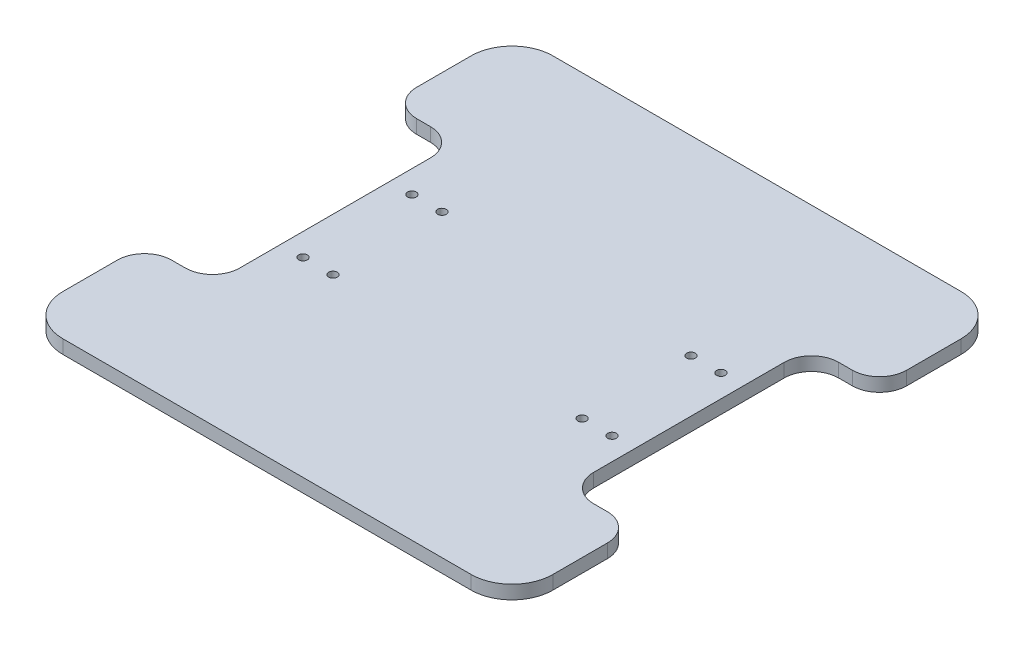
SolidWorks part; units mm, degrees
ref_plane "Спереди" through (0, 0, 0) normal (0, 0, 1) x (1, 0, 0)
ref_plane "Сверху" through (0, 0, 0) normal (0, 1, 0) x (1, 0, 0)
ref_plane "Справа" through (0, 0, 0) normal (1, 0, 0) x (0, 0, -1)
sketch "Sketch1" plane through (0, 0, 0) normal (0, 1, 0) x (1, 0, 0)
  line L1 (-90, 90) -> (90, 90)
  line L2 (-90, 90) -> (-90, -90)
  line L3 (-90, -90) -> (90, -90)
  line L4 (90, 90) -> (90, -90)
  line L5 (-90, 90) -> (90, -90) construction
  line L6 (-90, -90) -> (90, 90) construction
  point P0 (0, 0)
  dimension "D1" = 180
  dimension "D2" = 180
extrude "Boss-Extrude1" add sketch "Sketch1" along normal blind 5
fillet "Fillet1" radius 15 4 edges at (-90, 2.5, -90) (90, 2.5, -90) (-90, 2.5, 90) (90, 2.5, 90)
sketch "Sketch2" plane through (0, 5, 0) normal (0, 1, 0) x (1, 0, 0)
  line L0 (0, 0) -> (-77.5, 0) construction
  line L1 (2.75, 0) -> (-2.75, 0) construction
  line L2 (-90, 75) -> (-90, -75) construction
  line L3 (-90, 45) -> (-65, 45)
  line L4 (-90, 45) -> (-90, -45)
  line L5 (-90, -45) -> (-65, -45)
  line L6 (-65, 45) -> (-65, -45)
  line L7 (-90, 45) -> (-65, -45) construction
  line L8 (-90, -45) -> (-65, 45) construction
  line L9 (0, 0) -> (0, 45) construction
  line L10 (90, -45) -> (65, 45) construction
  line L11 (90, 45) -> (65, -45) construction
  line L12 (65, 45) -> (65, -45)
  line L13 (90, -45) -> (65, -45)
  line L14 (90, 45) -> (90, -45)
  line L15 (90, 45) -> (65, 45)
  circle A0 centre (-56.75, 20) radius 1.6
  circle A1 centre (-45.75, 20) radius 1.6
  circle A2 centre (-56.75, -20) radius 1.6
  circle A3 centre (-45.75, -20) radius 1.6
  circle A4 centre (45.75, 20) radius 1.6
  circle A5 centre (56.75, 20) radius 1.6
  circle A6 centre (45.75, -20) radius 1.6
  circle A7 centre (56.75, -20) radius 1.6
  dimension "D1" = 25
  dimension "D2" = 90
extrude "Cut-Extrude2" cut sketch "Sketch2" against normal through all
fillet "Fillet2" radius 10 8 edges at (-65, 2.5, 45) (-65, 2.5, -45) (65, 2.5, -45) (65, 2.5, 45) (90, 2.5, -45) (90, 2.5, 45) (-90, 2.5, 45) (-90, 2.5, -45)
